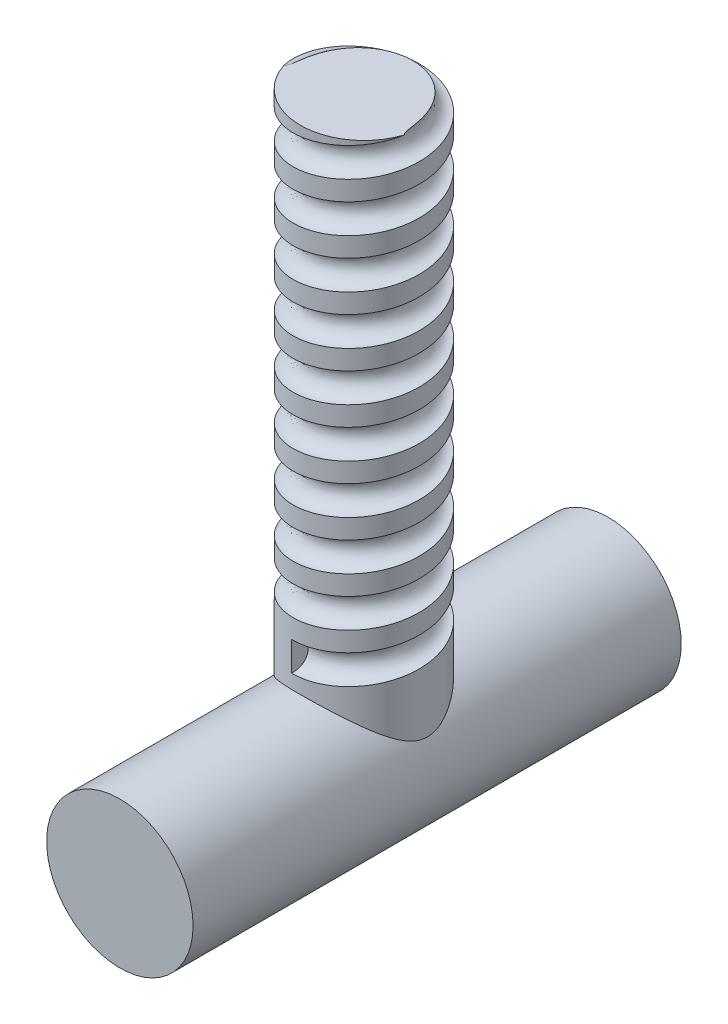
SolidWorks part; units mm, degrees
material "1.0558 (G300)"
ref_plane "Ön Düzlem" through (0, 0, 0) normal (0, 0, 1) x (1, 0, 0)
ref_plane "Üst Düzlem" through (0, 0, 0) normal (0, 1, 0) x (1, 0, 0)
ref_plane "Sağ Düzlem" through (0, 0, 0) normal (1, 0, 0) x (0, 0, -1)
sketch "Çizim1" plane through (0, 0, 0) normal (0, 0, 1) x (1, 0, 0)
  circle A0 centre (0, 0) radius 7.5
  dimension "D1" = 15
extrude "Yükseklik-Ekstrüzyon1" add sketch "Çizim1" along normal mid plane 50
sketch "Çizim2" plane through (0, 0, 0) normal (0, 1, 0) x (1, 0, 0)
  circle A0 centre (0, 0) radius 6.5
  dimension "D1" = 13
extrude "Yükseklik-Ekstrüzyon2" add sketch "Çizim2" along normal blind 58
sketch "Çizim3" plane through (0, 58, 0) normal (0, 1, 0) x (1, 0, 0)
  circle A1 centre (0, 0) radius 6.5
  circle A2 centre (0, 0) radius 6.5
  dimension "D1" = 0
curve "Helis/Spiral1" pitch 5 height 52 turns 10.4
sketch "Çizim4" plane through (0, 0, 0) normal (1, 0, 0) x (0, 0, -1)
  circle A0 centre (6.5, 58) radius 1.5
  dimension "D1" = 3
sweep "Kes-Süpür1" cut profiles "Çizim4" path "Helis/Spiral1"
